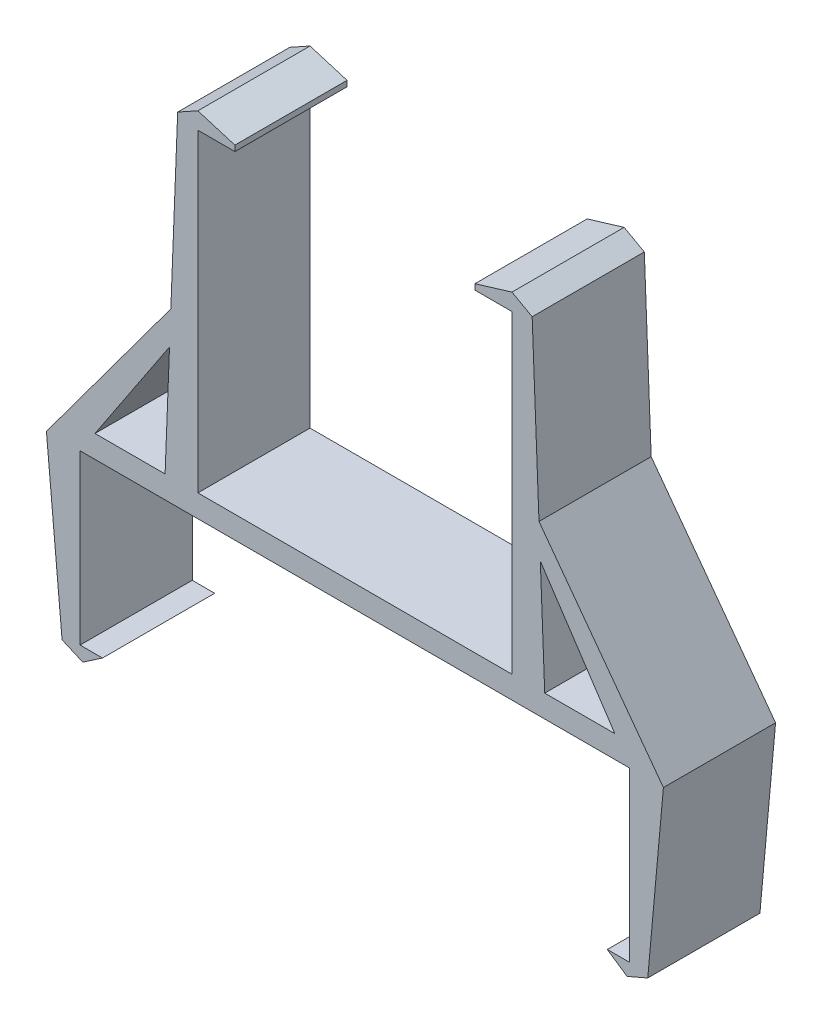
SolidWorks part; units mm, degrees
ref_plane "Ebene vorne" through (0, 0, 0) normal (0, 0, 1) x (1, 0, 0)
ref_plane "Ebene oben" through (0, 0, 0) normal (0, 1, 0) x (1, 0, 0)
ref_plane "Ebene rechts" through (0, 0, 0) normal (1, 0, 0) x (0, 0, -1)
sketch "Skizze1" plane through (0, 0, 0) normal (0, 0, 1) x (1, 0, 0)
  line L0 (-1.8, 28.5) -> (0, 29.5)
  line L1 (0, 0) -> (28, 0)
  line L2 (0, 0) -> (0, 28)
  line L3 (0, 28) -> (3.3, 28)
  line L4 (28, 0) -> (28, 28)
  line L5 (28, 28) -> (24.7, 28)
  line L6 (3.3, 28) -> (0, 28)
  line L7 (-1.8, 28.5) -> (-3, -2)
  line L8 (-3, -2) -> (31, -2)
  line L9 (14, 0) -> (14, -8.0454) construction
  line L10 (29.8, 28.5) -> (31, -2)
  line L11 (24.7, 28) -> (28, 28)
  line L13 (28, 0) -> (28, 28)
  line L14 (29.8, 28.5) -> (28, 29.5)
  line L15 (24.7, 28) -> (28, 28)
  line L16 (-10.5, -2) -> (38.5, -2)
  line L17 (-10.5, -2) -> (-10.5, -17)
  line L18 (-12.2321, -16) -> (-12.1053, -17.4)
  line L19 (-12.1053, -17.4) -> (-10.2579, -18.2)
  line L20 (-10.2579, -18.2) -> (-8.5, -17)
  line L21 (-12.2321, -16) -> (-13.5, -2)
  line L22 (-13.5, -2) -> (-2.4098, 13)
  line L23 (41.5, -2) -> (30.4098, 13)
  line L24 (38.5, -2) -> (38.5, -17)
  line L25 (40.2321, -16) -> (41.5, -2)
  line L26 (40.2321, -16) -> (41.5, -2)
  line L27 (36.5, -17) -> (38.5, -17)
  line L28 (38.5, -2) -> (38.5, -17)
  line L29 (29.8, 28.5) -> (31, -2)
  line L30 (-2.4098, 13) -> (-3, -2)
  line L31 (-8.5, -17) -> (-10.5, -17)
  line L32 (-12.2321, -16) -> (-13.5, -2)
  line L33 (-2.4098, 13) -> (-13.5, -2)
  line L34 (-12.2321, -16) -> (-13.5, -2)
  line L35 (-10.5, -2) -> (-10.5, -17)
  line L36 (-9.1283, 0) -> (-4.4, 0)
  line L37 (-2.5279, 10) -> (-10.5, -2)
  line L38 (-4.4, 0) -> (-2.9213, 0)
  line L39 (30.5279, 10) -> (38.5, -2)
  line L40 (32.4, 0) -> (30.9213, 0)
  line L41 (37.1283, 0) -> (32.4, 0)
  line L42 (40.2321, -16) -> (41.5, -2)
  line L43 (38.2579, -18.2) -> (36.5, -17)
  line L44 (40.1053, -17.4) -> (38.2579, -18.2)
  line L45 (40.2321, -16) -> (40.1053, -17.4)
  line L46 (38.5, -2) -> (38.5, -17)
  line L47 (-9.1713, 0) -> (-9.1283, 0)
  line L48 (37.1713, 0) -> (37.1283, 0)
  line L49 (3.3, 28) -> (3.3, 28.5)
  line L50 (3.3, 28.5) -> (0, 29.5)
  line L51 (24.7, 28) -> (24.7, 28.5)
  line L52 (24.7, 28.5) -> (28, 29.5)
  arc A0 (-10.5, -2) -> (-13.4454, -2.6026) centre (-10.5, -9.5) ccw
  point P16 (14, -2)
  point P19 (14, -2)
  dimension "D1" = 28
  dimension "D2" = 28
  dimension "D3" = 2
  dimension "D4" = 3.3
  dimension "D5" = 1.5
  dimension "D6" = 0.5
  dimension "D7" = 3
  dimension "D8" = 1.8
  dimension "D9" = 49
  dimension "D10" = 15
  dimension "D11" = 14
  dimension "D12" = 2
  dimension "D13" = 0
  dimension "D14" = 3
  dimension "D15" = 15
  dimension "D16" = 3
  dimension "D17" = 2
  dimension "D18" = 1.2
  dimension "D19" = 0.4
extrude "Aufsatz-Linear austragen1" add sketch "Skizze1" along normal blind 10 contours L9 L1 L2 L3 L0 L7 L8 | L1 L9 L8 L10 L14 L11 L4 region at (-0.7262, 28.6871, 0) region at (14.3579, -1, 0)
extrude "Aufsatz-Linear austragen2" add sketch "Skizze1<3>" along normal blind 10 contours A0 L16 L7 L22 L21 | L17 A0 L34 | A0 L21 | L45 L25 L23 L10 L39 L24 L27 L43 L44 region at (-7.6739, 4.2199, 0) region at (-11.5918, -9.4733, 0) region at (38.1115, -0.8168, 0)
sketch "Skizze1<3>" plane through (0, 0, 0) normal (0, 0, 1) x (1, 0, 0) same geometry as "Skizze1"
extrude "Aufsatz-Linear austragen3" add sketch "Skizze1<4>" along normal blind 10 contours L38 L36 L37 L16 L7 | L39 L41 L40 L10 L16 region at (-6.4088, -1.0303, 0) region at (34.4088, -1.0303, 0)
sketch "Skizze1<4>" plane through (0, 0, 0) normal (0, 0, 1) x (1, 0, 0) same geometry as "Skizze1"
